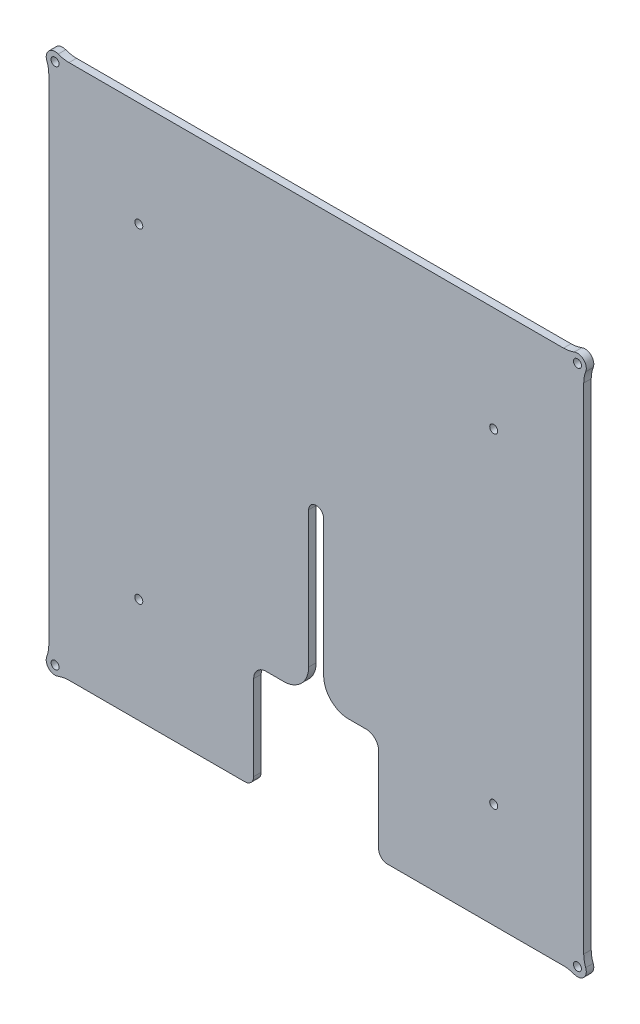
SolidWorks part; units mm, degrees
material "Balsa"
ref_plane "Front Plane" through (0, 0, 0) normal (0, 0, 1) x (1, 0, 0)
ref_plane "Top Plane" through (0, 0, 0) normal (0, 1, 0) x (1, 0, 0)
ref_plane "Right Plane" through (0, 0, 0) normal (1, 0, 0) x (0, 0, -1)
sketch "Sketch1" plane through (0, 0, 0) normal (0, 0, 1) x (1, 0, 0)
  line L0 (-107, 98.923) -> (-107, -98.923)
  line L1 (98.923, 107) -> (-98.923, 107)
  line L2 (107, -98.923) -> (107, 98.923)
  line L3 (43, -107) -> (98.923, -107)
  line L4 (43, -107) -> (43, -101) construction
  line L5 (39, -97) -> (-39, -97) construction
  line L6 (-43, -101) -> (-43, -107) construction
  line L7 (-98.923, -107) -> (-43, -107)
  line L8 (-43, -107) -> (43, -107)
  line L9 (104.5, -104.5) -> (-104.5, -104.5) construction
  line L10 (104.5, -104.5) -> (104.5, 104.5) construction
  line L11 (104.5, 104.5) -> (-104.5, 104.5) construction
  line L12 (-104.5, -104.5) -> (-104.5, 104.5) construction
  line L13 (104.5, -104.5) -> (-104.5, 104.5) construction
  line L14 (104.5, 104.5) -> (-104.5, -104.5) construction
  circle A0 centre (-104.5, -104.5) radius 1.6
  circle A1 centre (-104.5, 104.5) radius 1.6
  circle A2 centre (104.5, 104.5) radius 1.6
  circle A3 centre (104.5, -104.5) radius 1.6
  arc A4 (43, -101) -> (39, -97) centre (39, -101) ccw construction
  arc A5 (-39, -97) -> (-43, -101) centre (-39, -101) ccw construction
  arc A6 (-103.2308, 107.7999) -> (-107.7999, 103.2308) centre (-104.5, 104.5) ccw
  arc A8 (-107.7999, -103.2308) -> (-103.2308, -107.7999) centre (-104.5, -104.5) ccw
  arc A9 (98.923, -107) -> (103.2308, -107.7999) centre (98.923, -119) cw
  arc A10 (103.2308, -107.7999) -> (107.7999, -103.2308) centre (104.5, -104.5) ccw
  arc A13 (107.7999, 103.2308) -> (103.2308, 107.7999) centre (104.5, 104.5) ccw
  arc A14 (107, -98.923) -> (107.7999, -103.2308) centre (119, -98.923) ccw
  arc A15 (-103.2308, -107.7999) -> (-98.923, -107) centre (-98.923, -119) cw
  arc A16 (-107, -98.923) -> (-107.7999, -103.2308) centre (-119, -98.923) cw
  arc A17 (-107.7999, 103.2308) -> (-107, 98.923) centre (-119, 98.923) cw
  arc A18 (-103.2308, 107.7999) -> (-98.923, 107) centre (-98.923, 119) ccw
  arc A19 (107, 98.923) -> (107.7999, 103.2308) centre (119, 98.923) cw
  arc A20 (103.2308, 107.7999) -> (98.923, 107) centre (98.923, 119) cw
  point P0 (0, 0)
  dimension "D1" = 12
  dimension "D3" = 12
  dimension "D4" = 12
  dimension "D5" = 12
  dimension "D6" = 12
  dimension "D7" = 12
  dimension "D2" = 209
  dimension "D8" = 214
  dimension "D9" = 10
extrude "Boss-Extrude1" add sketch "Sketch1" along normal blind 3
sketch "Sketch3" plane through (0, 0, 3) normal (0, 0, 1) x (1, 0, 0)
  line L0 (-107, 98.923) -> (-107, -98.923) construction
  line L1 (71, -65) -> (-71, -65) construction
  line L2 (71, -65) -> (71, 65) construction
  line L3 (71, 65) -> (-71, 65) construction
  line L4 (-71, -65) -> (-71, 65) construction
  line L5 (71, -65) -> (-71, 65) construction
  line L6 (71, 65) -> (-71, -65) construction
  line L8 (98.923, 107) -> (-98.923, 107) construction
  circle A0 centre (-71, 65) radius 1.6
  circle A1 centre (71, 65) radius 1.6
  circle A2 centre (71, -65) radius 1.6
  circle A3 centre (-71, -65) radius 1.6
  point P0 (0, 0)
  dimension "D3" = 3.2
  dimension "D1" = 36
  dimension "D2" = 130
extrude "Cut-Extrude2" cut sketch "Sketch3" against normal through all
sketch "Sketch5" plane through (0, 0, 0) normal (0, 0, 1) x (1, 0, 0)
  line L0 (-107, 0) -> (107, 0) construction
  line L1 (-107, 98.923) -> (-107, -98.923) construction
  line L2 (107, -98.923) -> (107, 98.923) construction
  line L3 (-98.923, -107) -> (98.923, -107) construction
  line L4 (-25.0334, -107) -> (24.9666, -107)
  line L12 (2.9666, 0) -> (2.9666, -54.5)
  line L13 (-3.0334, 0) -> (-3.0334, -54.5)
  line L14 (-13.0334, -64.5) -> (-20.0334, -64.5)
  line L15 (-25.0334, -69.5) -> (-25.0334, -107)
  line L16 (19.9666, -112) -> (-20.0334, -112) construction
  line L17 (24.9666, -69.5) -> (24.9666, -107)
  line L18 (19.9666, -64.5) -> (12.9666, -64.5)
  line L19 (-0.0334, 0) -> (-0.0334, -112) construction
  arc A15 (2.9666, -54.5) -> (12.9666, -64.5) centre (12.9666, -54.5) ccw
  arc A16 (2.9666, 0) -> (-3.0334, 0) centre (-0.0334, 0) ccw
  arc A17 (-13.0334, -64.5) -> (-3.0334, -54.5) centre (-13.0334, -54.5) ccw
  arc A18 (-20.0334, -64.5) -> (-25.0334, -69.5) centre (-20.0334, -69.5) ccw
  arc A19 (-25.0334, -107) -> (-20.0334, -112) centre (-20.0334, -107) ccw construction
  arc A20 (19.9666, -112) -> (24.9666, -107) centre (19.9666, -107) ccw construction
  arc A21 (24.9666, -69.5) -> (19.9666, -64.5) centre (19.9666, -69.5) ccw
  dimension "D5" = 10
  dimension "D6" = 5
  dimension "D1" = 50
  dimension "D2" = 64.5
extrude "Cut-Extrude5" cut sketch "Sketch5" along normal through all
fillet "Fillet1" radius 3.54 2 edges at (-25.0334, -107, 1.5) (24.9666, -107, 1.5)
